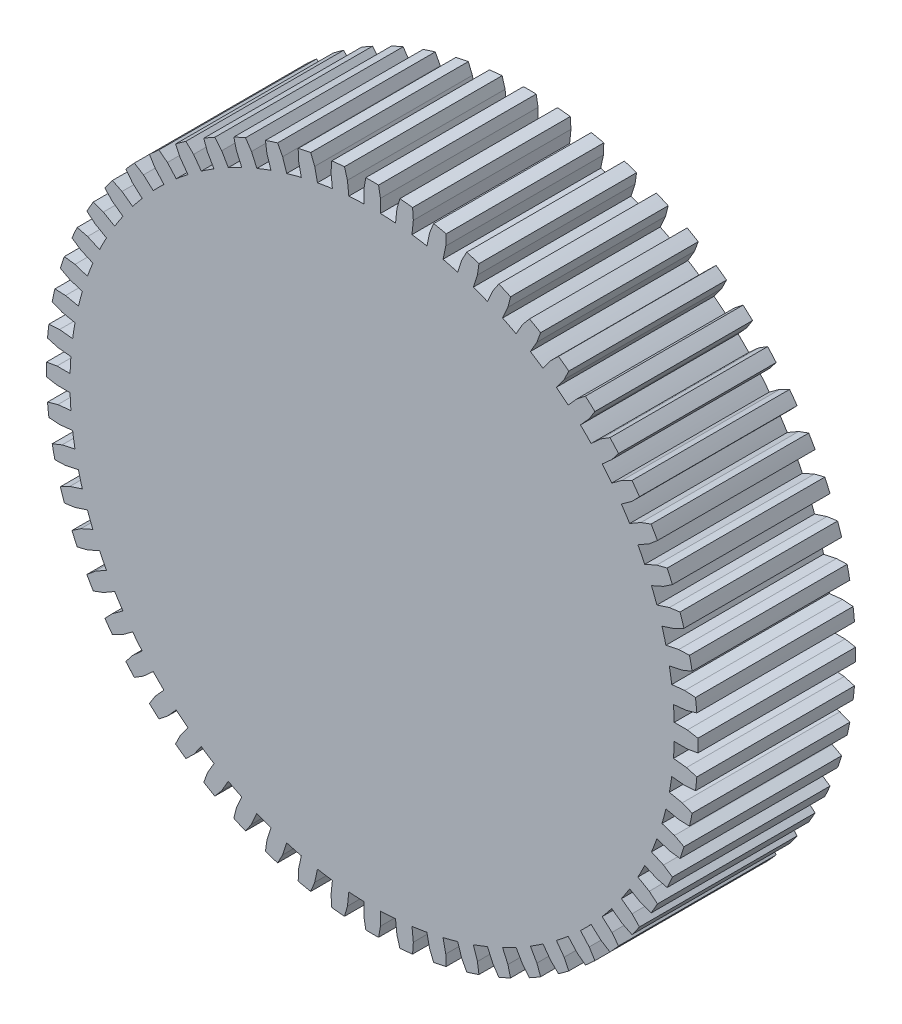
SolidWorks part; units mm, degrees
ref_plane "Plan de face" through (0, 0, 0) normal (0, 0, 1) x (1, 0, 0)
ref_plane "Plan de dessus" through (0, 0, 0) normal (0, 1, 0) x (1, 0, 0)
ref_plane "Plan de droite" through (0, 0, 0) normal (1, 0, 0) x (0, 0, -1)
sketch "Esquisse1" plane through (0, 0, 0) normal (0, 0, 1) x (1, 0, 0)
  line L0 (0, 56.7772) -> (0, -41.8125) construction
  line L1 (-1.5708, 57.4785) -> (-1.5708, 59.9794)
  line L2 (-1.5708, 59.9794) -> (-1.2166, 61.9881)
  line L3 (1.5708, 57.4785) -> (1.5708, 59.9794)
  line L4 (1.5708, 59.9794) -> (1.2166, 61.9881)
  arc A0 (-1.5708, 57.4785) -> (1.5708, 57.4785) centre (0, 0) ccw
  circle A1 centre (0, 0) radius 60 construction
  circle A2 centre (0, 0) radius 62 construction
  arc A3 (-1.2166, 61.9881) -> (1.2166, 61.9881) centre (0, 0) cw
  dimension "Df" = 115
  dimension "D" = 120
  dimension "Da" = 124
  dimension "EP" = 3.1416
  dimension "teta" = 20
extrude "Boss.-Extru.1" add sketch "Esquisse1" along normal blind 30
pattern_circular "Répétition circulaire1" count 60 over 360 about axis through (0, 0, 30) along (0, 0, -1) of "Boss.-Extru.1"
